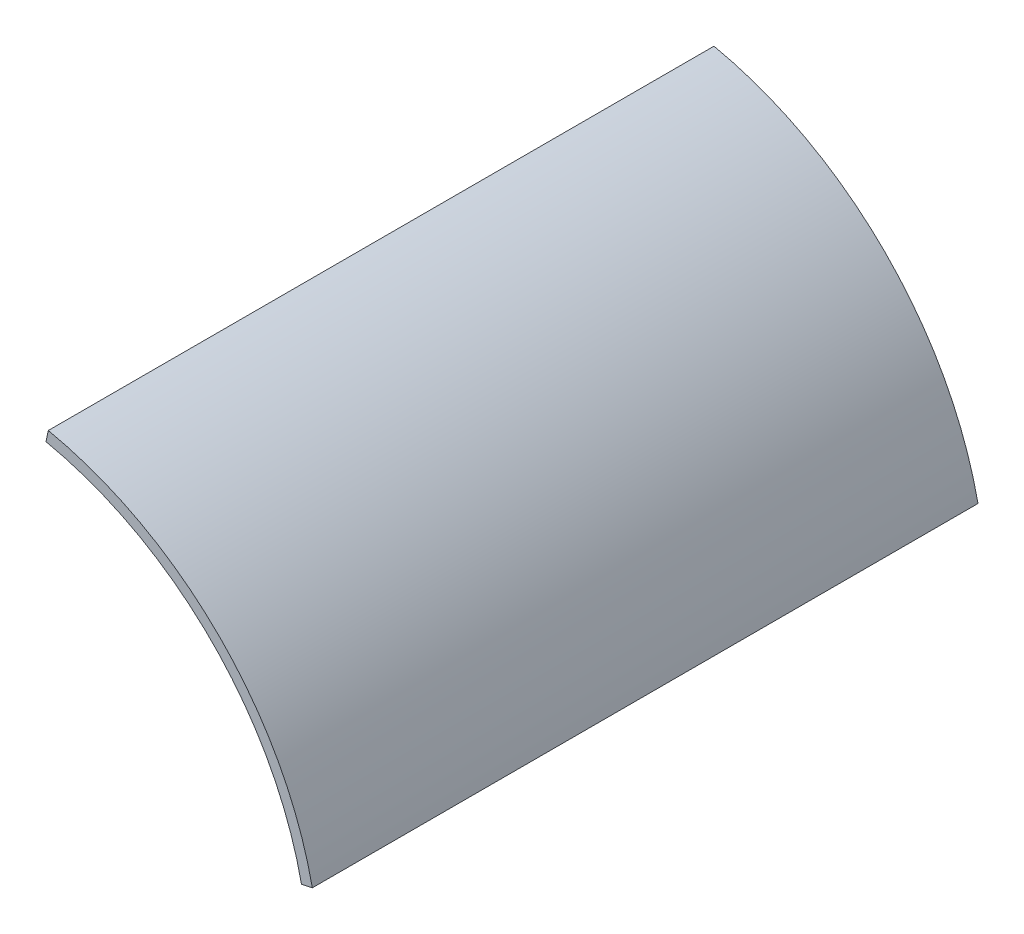
SolidWorks part; units mm, degrees
material "ABS"
ref_plane "Alzado" through (0, 0, 0) normal (0, 0, 1) x (1, 0, 0)
ref_plane "Planta" through (0, 0, 0) normal (0, 1, 0) x (1, 0, 0)
ref_plane "Vista lateral" through (0, 0, 0) normal (1, 0, 0) x (0, 0, -1)
sketch "Croquis1" plane through (0, 0, 0) normal (0, 0, 1) x (1, 0, 0)
  line L0 (0, 0) -> (0, 58) construction
  line L1 (0, 0) -> (58, 0) construction
  line L2 (0, 0) -> (30.2248, 6.4245) construction
  line L3 (0, 0) -> (6.4245, 30.2248) construction
  line L4 (6.4245, 30.2248) -> (6.2166, 29.2466)
  line L5 (30.2248, 6.4245) -> (29.2466, 6.2166)
  arc A0 (6.2166, 29.2466) -> (29.2466, 6.2166) centre (0, 0) cw
  arc A1 (30.2248, 6.4245) -> (6.4245, 30.2248) centre (0, 0) ccw
  dimension "D1" = 29.9
  dimension "D2" = 1
  dimension "D3" = 12
  dimension "D4" = 12
extrude "Saliente-Extruir1" add sketch "Croquis1" along normal blind 60
